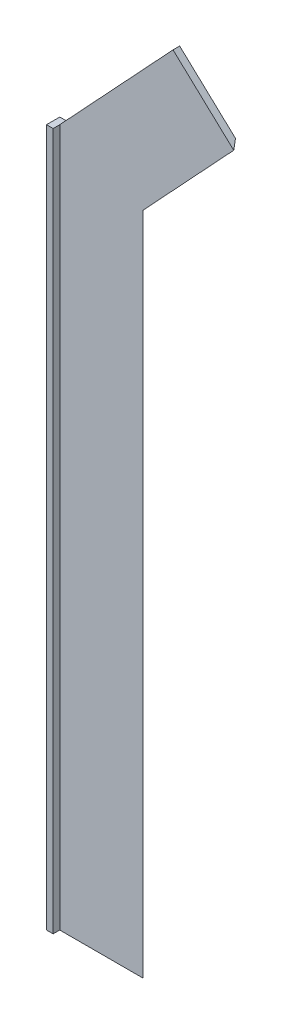
SolidWorks part; units mm, degrees
ref_plane "Front Plane" through (0, 0, 0) normal (0, 0, 1) x (1, 0, 0)
ref_plane "Top Plane" through (0, 0, 0) normal (0, 1, 0) x (1, 0, 0)
ref_plane "Right Plane" through (0, 0, 0) normal (1, 0, 0) x (0, 0, -1)
sketch "Sketch2" plane through (0, 0, 0) normal (0, 0, 1) x (1, 0, 0)
  line L0 (0, 0) -> (0, 297) construction
  line L1 (0, 297) -> (210, 297) construction
  line L2 (210, 297) -> (210, 0) construction
  line L3 (210, 0) -> (0, 0) construction
  dimension "D1" = 210
  dimension "D2" = 297
sketch "Sketch3" plane through (0, 0, 0) normal (0, 0, 1) x (1, 0, 0)
  line L0 (0, 297) -> (210, 297) construction
  line L1 (0, 50.4323) -> (25, 50.4323)
  line L2 (0, 50.4323) -> (0, 260.4323)
  line L3 (34.0999, 297) -> (52.3838, 279.95)
  line L4 (25, 50.4323) -> (25, 250.5846)
  line L5 (0, 260.4323) -> (34.0999, 297)
  line L6 (25, 250.5846) -> (52.3838, 279.95)
  line L7 (0, 260.4323) -> (25, 250.5846) construction
  dimension "D2" = 27.3838
  dimension "D3" = 68.5
  dimension "D4" = 50
  dimension "D5" = 36.5677
  dimension "D6" = 210
extrude "Boss-Extrude1" add sketch "Sketch3" along normal blind 2
sketch "Sketch4" plane through (0, 0, 0) normal (-1, 0, 0) x (0, 0, 1)
  line L1 (0, 260.4323) -> (4, 260.4323)
  line L2 (0, 260.4323) -> (0, 50.4323)
  line L3 (0, 50.4323) -> (4, 50.4323)
  line L4 (4, 260.4323) -> (4, 50.4323)
  dimension "D1" = 4
extrude "Boss-Extrude2" add sketch "Sketch4" along normal blind 2
chamfer "Chamfer1" distance 2 angle 45 2 edges at (38.6919, 265.2673, 0) (25, 150.5084, 0)
